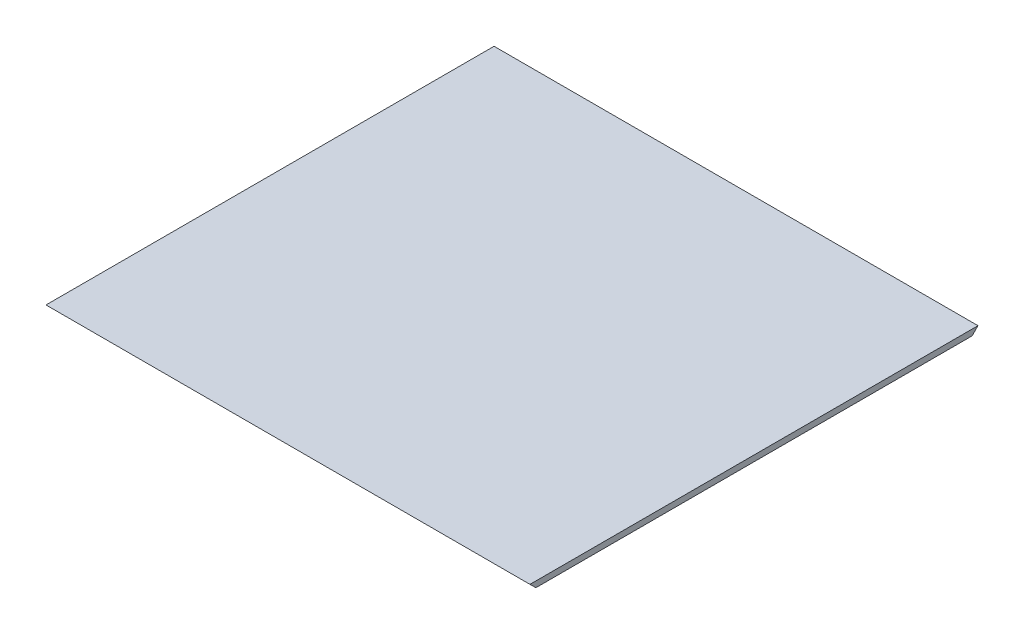
SolidWorks part; units mm, degrees
ref_plane "Front Plane" through (0, 0, 0) normal (0, 0, 1) x (1, 0, 0)
ref_plane "Top Plane" through (0, 0, 0) normal (0, 1, 0) x (1, 0, 0)
ref_plane "Right Plane" through (0, 0, 0) normal (1, 0, 0) x (0, 0, -1)
sketch "Sketch1" plane through (0, 0, 0) normal (0, 1, 0) x (1, 0, 0)
  line L1 (-130.175, -120.523) -> (130.175, -120.523)
  line L2 (-130.175, -120.523) -> (-130.175, 120.523)
  line L3 (-130.175, 120.523) -> (130.175, 120.523)
  line L4 (130.175, -120.523) -> (130.175, 120.523)
  line L5 (-130.175, -120.523) -> (130.175, 120.523) construction
  line L6 (-130.175, 120.523) -> (130.175, -120.523) construction
  point P0 (0, 0)
  dimension "D1" = 241.046
  dimension "D2" = 260.35
extrude "Boss-Extrude1" add sketch "Sketch1" along normal mid plane 3.175 contours L2 L3 L4 L1
sketch "Sketch3" plane through (-130.175, 0, 0) normal (-1, 0, 0) x (0, 0, 1)
  line L0 (120.523, 1.5875) -> (117.3168, -1.5875)
  line L2 (120.523, -1.5875) -> (-120.523, -1.5875) construction
  line L3 (117.3168, -1.5875) -> (181.7596, -66.6645)
  line L4 (181.7596, -66.6645) -> (184.9658, -63.4895)
  line L5 (-120.523, 1.5875) -> (-115.9365, -2.999)
  line L6 (-115.9365, -2.999) -> (-117.6909, -4.7534)
  line L7 (-117.6909, -4.7534) -> (-122.2774, -0.1669)
  line L8 (-122.2774, -0.1669) -> (-120.523, 1.5875)
  line L9 (184.9658, -63.4895) -> (120.523, 1.5875)
extrude "Cut-Extrude2" cut sketch "Sketch3" against normal through all
